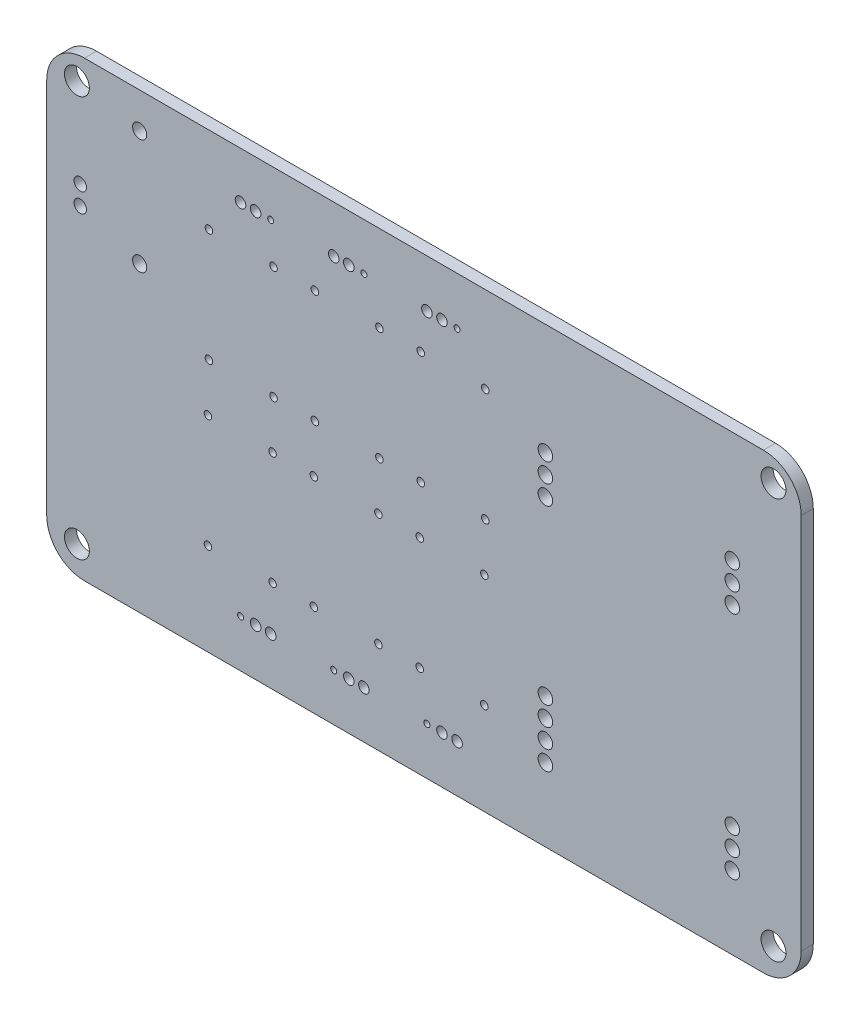
SolidWorks part; units mm, degrees
ref_plane "Front Plane" through (0, 0, 0) normal (0, 0, 1) x (1, 0, 0)
ref_plane "Top Plane" through (0, 0, 0) normal (0, 1, 0) x (1, 0, 0)
ref_plane "Right Plane" through (0, 0, 0) normal (1, 0, 0) x (0, 0, -1)
sketch "BoardOutLine" plane through (0, 0, 0) normal (0, 0, 1) x (1, 0, 0)
  line L0 (0, -55) -> (0, -5)
  line L1 (100, -5) -> (100, -55)
  line L2 (95, -60) -> (5, -60)
  line L3 (5, 0) -> (95, 0)
  line L4 (5, -5) -> (95, -55) construction
  line L6 (95, -5) -> (5, -55) construction
  arc A0 (100, -5) -> (95, 0) centre (95, -5) ccw
  arc A1 (0, -55) -> (5, -60) centre (5, -55) ccw
  arc A2 (5, 0) -> (0, -5) centre (5, -5) ccw
  arc A3 (95, -60) -> (100, -55) centre (95, -55) ccw
  dimension "D1" = 5
  dimension "D2" = 90
  dimension "D3" = 50
  dimension "D4" = 5
  dimension "D5" = 5
extrude "Boss-Extrude2" add sketch "BoardOutLine" along normal blind 1.6
sketch "Multi-Layer" plane through (0, 0, 1.6) normal (0, 0, 1) x (1, 0, 0)
  circle A1 centre (12.319, -4.699) radius 0.9398
  circle A3 centre (12.319, -19.939) radius 0.9398
  circle A5 centre (4.445, -14.732) radius 0.8255
  circle A7 centre (4.445, -17.272) radius 0.8255
  circle A10 centre (90.8641, -50.3084) radius 0.9652
  circle A13 centre (90.8641, -47.7684) radius 0.9652
  circle A16 centre (90.8641, -45.2283) radius 0.9652
  circle A46 centre (90.8641, -19.8283) radius 0.9652
  circle A49 centre (90.8641, -17.2883) radius 0.9652
  circle A52 centre (90.8641, -14.7483) radius 0.9652
  circle A55 centre (66.094, -14.7483) radius 0.9652
  circle A58 centre (66.094, -17.2883) radius 0.9652
  circle A61 centre (66.094, -19.8283) radius 0.9652
  circle A88 centre (66.094, -42.6883) radius 0.9652
  circle A91 centre (66.094, -45.2283) radius 0.9652
  circle A94 centre (66.094, -47.7684) radius 0.9652
  circle A97 centre (66.094, -50.3084) radius 0.9652
  circle A127 centre (40.0368, -6.223) radius 0.7
  circle A129 centre (38.0368, -6.223) radius 0.7
  circle A131 centre (52.3876, -6.35) radius 0.7
  circle A133 centre (50.3876, -6.35) radius 0.7
  circle A135 centre (40.0368, -53.7211) radius 0.7
  circle A137 centre (42.0368, -53.7211) radius 0.7
  circle A139 centre (52.3876, -53.7211) radius 0.7
  circle A141 centre (54.3876, -53.7211) radius 0.7
  circle A143 centre (27.6861, -6.223) radius 0.7
  circle A145 centre (25.6861, -6.223) radius 0.7
  circle A147 centre (27.6861, -53.7211) radius 0.7
  circle A149 centre (29.6861, -53.7211) radius 0.7
  circle A150 centre (44.0961, -11.4149) radius 0.5
  circle A151 centre (35.5373, -11.4149) radius 0.5
  circle A152 centre (44.0961, -26.3802) radius 0.5
  circle A153 centre (35.5373, -26.3802) radius 0.5
  circle A154 centre (58.1296, -11.4149) radius 0.5
  circle A155 centre (49.5708, -11.4149) radius 0.5
  circle A156 centre (58.1296, -26.3802) radius 0.5
  circle A157 centre (49.5708, -26.3802) radius 0.5
  circle A158 centre (30.0626, -11.4149) radius 0.5
  circle A159 centre (21.5038, -11.4149) radius 0.5
  circle A160 centre (30.0626, -26.3802) radius 0.5
  circle A161 centre (21.5038, -26.3802) radius 0.5
  circle A162 centre (49.4396, -47.7672) radius 0.5
  circle A163 centre (57.9984, -47.7672) radius 0.5
  circle A164 centre (49.4396, -32.802) radius 0.5
  circle A165 centre (57.9984, -32.802) radius 0.5
  circle A166 centre (35.406, -47.7672) radius 0.5
  circle A167 centre (43.9648, -47.7672) radius 0.5
  circle A168 centre (35.406, -32.802) radius 0.5
  circle A169 centre (43.9648, -32.802) radius 0.5
  circle A170 centre (21.3725, -47.7672) radius 0.5
  circle A171 centre (29.9313, -47.7672) radius 0.5
  circle A172 centre (21.3725, -32.802) radius 0.5
  circle A173 centre (29.9313, -32.802) radius 0.5
  circle A181 centre (42.0368, -6.223) radius 0.4
  circle A182 centre (54.3876, -6.35) radius 0.4
  circle A183 centre (38.0368, -53.7211) radius 0.4
  circle A184 centre (50.3876, -53.7211) radius 0.4
  circle A185 centre (29.6861, -6.223) radius 0.4
  circle A186 centre (25.6861, -53.7211) radius 0.4
  circle A187 centre (96.3297, -3.1115) radius 1.65
  circle A188 centre (4.0005, -3.1115) radius 1.65
  circle A189 centre (96.3297, -56.2611) radius 1.65
  circle A190 centre (4.0005, -56.2611) radius 1.65
  point P1 (0, 0)
  point P4 (0, 0)
  point P12 (0, 0)
  point P15 (0, 0)
  point P20 (0, 0)
  point P23 (0, 0)
  point P28 (0, 0)
  point P108 (0, 0)
  point P116 (0, 0)
  point P220 (0, 0)
  point P223 (0, 0)
  point P228 (0, 0)
  point P231 (0, 0)
  point P236 (0, 0)
  point P239 (0, 0)
  point P244 (0, 0)
  point P307 (0, 0)
  point P310 (0, 0)
  point P325 (0, 0)
extrude "Cut-Extrude2" cut sketch "Multi-Layer" against normal up to next (1.6 mm away)
sketch "BottomLayer" plane through (0, 0, 0) normal (0, 0, 1) x (1, 0, 0)
  line L0 (65.2082, -47.5949) -> (65.3816, -47.7684)
  line L2 (49.5708, -11.4148) -> (52.4663, -11.4148)
  line L3 (52.4663, -11.4148) -> (54.3876, -9.4935)
  line L4 (54.3876, -9.4935) -> (54.3876, -6.35)
  line L5 (29.9313, -32.8019) -> (30.5944, -34.4044)
  line L6 (30.5944, -34.4044) -> (32.8931, -36.7031)
  line L7 (32.8931, -36.7031) -> (42.2911, -36.7031)
  line L8 (42.2911, -36.7031) -> (43.3071, -35.6871)
  line L9 (43.3071, -35.6871) -> (43.9648, -32.8019)
  line L10 (43.9648, -32.8019) -> (44.0691, -35.6871)
  line L11 (44.0691, -35.6871) -> (44.9581, -36.7031)
  line L12 (44.9581, -36.7031) -> (56.1341, -36.7031)
  line L13 (56.1341, -36.7031) -> (58.0391, -34.5441)
  line L14 (58.0391, -34.5441) -> (57.9984, -32.8019)
  line L15 (29.9313, -47.7673) -> (27.1628, -47.7673)
  line L16 (27.1628, -47.7673) -> (25.6871, -49.2431)
  line L17 (25.6871, -49.2431) -> (25.6871, -53.7211)
  line L18 (57.9984, -47.7673) -> (53.5789, -47.7673)
  line L19 (53.5789, -47.7673) -> (50.3886, -50.9576)
  line L20 (50.3886, -50.9576) -> (50.3886, -53.7211)
  line L21 (49.5708, -26.3802) -> (49.5708, -11.4148)
  line L22 (57.9984, -47.7673) -> (57.9984, -32.8019)
  line L23 (43.9648, -32.8019) -> (43.9648, -47.7673)
  line L24 (29.9313, -47.7673) -> (29.9313, -32.8019)
  line L25 (35.5373, -26.3802) -> (38.3312, -23.114)
  line L26 (38.3312, -23.114) -> (46.0224, -23.114)
  line L27 (46.0224, -23.114) -> (49.5708, -26.3802)
  line L28 (21.5038, -26.3802) -> (24.8692, -22.352)
  line L29 (24.8692, -22.352) -> (31.0363, -22.352)
  line L30 (31.0363, -22.352) -> (35.5373, -26.3802)
  line L31 (35.5373, -26.3802) -> (35.5373, -11.4148)
  line L32 (21.5038, -26.3802) -> (21.5038, -11.4148)
  line L33 (57.9984, -47.7673) -> (57.9994, -47.7684)
  line L34 (57.9994, -47.7684) -> (66.094, -47.7684)
  line L35 (52.3876, -53.7211) -> (52.3876, -52.1336)
  line L36 (52.3876, -52.1336) -> (54.2129, -50.3084)
  line L37 (54.2129, -50.3084) -> (66.094, -50.3084)
  line L38 (21.5038, -26.3802) -> (16.5456, -26.3805)
  line L39 (16.5456, -26.3805) -> (14.5568, -28.3693)
  line L40 (14.5568, -28.3693) -> (14.5568, -29.7816)
  line L41 (14.5568, -29.7816) -> (14.5568, -31.4478)
  line L42 (14.5568, -31.4478) -> (19.304, -36.1951)
  line L43 (19.304, -36.1951) -> (28.0467, -36.1951)
  line L44 (28.0467, -36.1951) -> (29.9416, -34.3002)
  line L45 (29.9416, -34.3002) -> (29.9313, -32.8019)
  line L46 (14.5568, -29.7816) -> (4.445, -19.6694)
  line L47 (4.445, -19.6694) -> (4.445, -17.272)
  line L48 (21.5038, -11.4148) -> (26.0503, -11.4148)
  line L49 (26.0503, -11.4148) -> (29.685, -7.78)
  line L50 (29.685, -7.78) -> (29.685, -6.223)
  line L51 (43.9648, -47.7673) -> (40.2438, -47.7673)
  line L52 (40.2438, -47.7673) -> (38.1001, -50.2921)
  line L53 (38.1001, -50.2921) -> (38.0368, -53.7211)
  line L54 (35.5373, -11.4148) -> (39.2583, -11.4148)
  line L55 (39.2583, -11.4148) -> (42.0371, -8.636)
  line L56 (42.0371, -8.636) -> (42.0371, -6.223)
sketch "BottomSilkLayer" plane through (0, 0, 0) normal (0, 0, 1) x (1, 0, 0)
  line L0 (82.4232, -18.034) -> (82.4232, -44.5136) construction
  line L1 (78.6132, -22.225) -> (78.6132, -40.5131) construction
  text T0 "Manipulator Board V1" font "ARIAL" height 2.032
  text T1 "Tamir Mhabary" font "ARIAL" height 2.032
sketch "BottomSolderMaskLayer" plane through (0, 0, 0) normal (0, 0, 1) x (1, 0, 0)
  line L0 (90.351, -50.3081) -> (90.351, -50.3084)
  line L1 (90.351, -50.3084) -> (90.351, -50.3081)
  line L2 (91.377, -50.3081) -> (91.377, -50.3084)
  line L3 (91.377, -50.3084) -> (91.377, -50.3081)
  line L4 (90.351, -47.7681) -> (90.351, -47.7684)
  line L5 (90.351, -47.7684) -> (90.351, -47.7681)
  line L6 (91.377, -47.7681) -> (91.377, -47.7684)
  line L7 (91.377, -47.7684) -> (91.377, -47.7681)
  line L8 (90.351, -45.2281) -> (90.351, -45.2283)
  line L9 (90.351, -45.2283) -> (90.351, -45.2281)
  line L10 (91.377, -45.2281) -> (91.377, -45.2283)
  line L11 (91.377, -45.2283) -> (91.377, -45.2281)
  line L12 (90.351, -42.6881) -> (90.351, -42.6883)
  line L13 (90.351, -42.6883) -> (90.351, -42.6881)
  line L14 (91.377, -42.6881) -> (91.377, -42.6883)
  line L15 (91.377, -42.6883) -> (91.377, -42.6881)
  line L16 (90.351, -40.1481) -> (90.351, -40.1483)
  line L17 (90.351, -40.1483) -> (90.351, -40.1481)
  line L18 (91.377, -40.1481) -> (91.377, -40.1483)
  line L19 (91.377, -40.1483) -> (91.377, -40.1481)
  line L20 (90.351, -37.6081) -> (90.351, -37.6083)
  line L21 (90.351, -37.6083) -> (90.351, -37.6081)
  line L22 (91.377, -37.6081) -> (91.377, -37.6083)
  line L23 (91.377, -37.6083) -> (91.377, -37.6081)
  line L24 (90.351, -35.0681) -> (90.351, -35.0683)
  line L25 (90.351, -35.0683) -> (90.351, -35.0681)
  line L26 (91.377, -35.0681) -> (91.377, -35.0683)
  line L27 (91.377, -35.0683) -> (91.377, -35.0681)
  line L28 (90.351, -32.5281) -> (90.351, -32.5283)
  line L29 (90.351, -32.5283) -> (90.351, -32.5281)
  line L30 (91.377, -32.5281) -> (91.377, -32.5283)
  line L31 (91.377, -32.5283) -> (91.377, -32.5281)
  line L32 (90.351, -29.9881) -> (90.351, -29.9883)
  line L33 (90.351, -29.9883) -> (90.351, -29.9881)
  line L34 (91.377, -29.9881) -> (91.377, -29.9883)
  line L35 (91.377, -29.9883) -> (91.377, -29.9881)
  line L36 (90.351, -27.4481) -> (90.351, -27.4483)
  line L37 (90.351, -27.4483) -> (90.351, -27.4481)
  line L38 (91.377, -27.4481) -> (91.377, -27.4483)
  line L39 (91.377, -27.4483) -> (91.377, -27.4481)
  line L40 (90.351, -24.908) -> (90.351, -24.9083)
  line L41 (90.351, -24.9083) -> (90.351, -24.908)
  line L42 (91.377, -24.908) -> (91.377, -24.9083)
  line L43 (91.377, -24.9083) -> (91.377, -24.908)
  line L44 (90.351, -22.368) -> (90.351, -22.3683)
  line L45 (90.351, -22.3683) -> (90.351, -22.368)
  line L46 (91.377, -22.368) -> (91.377, -22.3683)
  line L47 (91.377, -22.3683) -> (91.377, -22.368)
  line L48 (90.351, -19.828) -> (90.351, -19.8283)
  line L49 (90.351, -19.8283) -> (90.351, -19.828)
  line L50 (91.377, -19.828) -> (91.377, -19.8283)
  line L51 (91.377, -19.8283) -> (91.377, -19.828)
  line L52 (90.351, -17.288) -> (90.351, -17.2883)
  line L53 (90.351, -17.2883) -> (90.351, -17.288)
  line L54 (91.377, -17.288) -> (91.377, -17.2883)
  line L55 (91.377, -17.2883) -> (91.377, -17.288)
  line L56 (90.351, -14.748) -> (90.351, -14.7483)
  line L57 (90.351, -14.7483) -> (90.351, -14.748)
  line L58 (91.377, -14.748) -> (91.377, -14.7483)
  line L59 (91.377, -14.7483) -> (91.377, -14.748)
  line L60 (65.5808, -14.748) -> (65.5808, -14.7483)
  line L61 (65.5808, -14.7483) -> (65.5808, -14.748)
  line L62 (66.6069, -14.748) -> (66.6069, -14.7483)
  line L63 (66.6069, -14.7483) -> (66.6069, -14.748)
  line L64 (65.5808, -17.288) -> (65.5808, -17.2883)
  line L65 (65.5808, -17.2883) -> (65.5808, -17.288)
  line L66 (66.6069, -17.288) -> (66.6069, -17.2883)
  line L67 (66.6069, -17.2883) -> (66.6069, -17.288)
  line L68 (65.5808, -19.828) -> (65.5808, -19.8283)
  line L69 (65.5808, -19.8283) -> (65.5808, -19.828)
  line L70 (66.6069, -19.828) -> (66.6069, -19.8283)
  line L71 (66.6069, -19.8283) -> (66.6069, -19.828)
  line L72 (65.5808, -22.368) -> (65.5808, -22.3683)
  line L73 (65.5808, -22.3683) -> (65.5808, -22.368)
  line L74 (66.6069, -22.368) -> (66.6069, -22.3683)
  line L75 (66.6069, -22.3683) -> (66.6069, -22.368)
  line L76 (65.5808, -24.908) -> (65.5808, -24.9083)
  line L77 (65.5808, -24.9083) -> (65.5808, -24.908)
  line L78 (66.6069, -24.908) -> (66.6069, -24.9083)
  line L79 (66.6069, -24.9083) -> (66.6069, -24.908)
  line L80 (65.5808, -27.4481) -> (65.5808, -27.4483)
  line L81 (65.5808, -27.4483) -> (65.5808, -27.4481)
  line L82 (66.6069, -27.4481) -> (66.6069, -27.4483)
  line L83 (66.6069, -27.4483) -> (66.6069, -27.4481)
  line L84 (65.5808, -29.9881) -> (65.5808, -29.9883)
  line L85 (65.5808, -29.9883) -> (65.5808, -29.9881)
  line L86 (66.6069, -29.9881) -> (66.6069, -29.9883)
  line L87 (66.6069, -29.9883) -> (66.6069, -29.9881)
  line L88 (65.5808, -32.5281) -> (65.5808, -32.5283)
  line L89 (65.5808, -32.5283) -> (65.5808, -32.5281)
  line L90 (66.6069, -32.5281) -> (66.6069, -32.5283)
  line L91 (66.6069, -32.5283) -> (66.6069, -32.5281)
  line L92 (65.5808, -35.0681) -> (65.5808, -35.0683)
  line L93 (65.5808, -35.0683) -> (65.5808, -35.0681)
  line L94 (66.6069, -35.0681) -> (66.6069, -35.0683)
  line L95 (66.6069, -35.0683) -> (66.6069, -35.0681)
  line L96 (65.5808, -37.6081) -> (65.5808, -37.6083)
  line L97 (65.5808, -37.6083) -> (65.5808, -37.6081)
  line L98 (66.6069, -37.6081) -> (66.6069, -37.6083)
  line L99 (66.6069, -37.6083) -> (66.6069, -37.6081)
  line L100 (65.5808, -40.1481) -> (65.5808, -40.1483)
  line L101 (65.5808, -40.1483) -> (65.5808, -40.1481)
  line L102 (66.6069, -40.1481) -> (66.6069, -40.1483)
  line L103 (66.6069, -40.1483) -> (66.6069, -40.1481)
  line L104 (65.5808, -42.6881) -> (65.5808, -42.6883)
  line L105 (65.5808, -42.6883) -> (65.5808, -42.6881)
  line L106 (66.6069, -42.6881) -> (66.6069, -42.6883)
  line L107 (66.6069, -42.6883) -> (66.6069, -42.6881)
  line L108 (65.5808, -45.2281) -> (65.5808, -45.2283)
  line L109 (65.5808, -45.2283) -> (65.5808, -45.2281)
  line L110 (66.6069, -45.2281) -> (66.6069, -45.2283)
  line L111 (66.6069, -45.2283) -> (66.6069, -45.2281)
  line L112 (65.5808, -47.7681) -> (65.5808, -47.7684)
  line L113 (65.5808, -47.7684) -> (65.5808, -47.7681)
  line L114 (66.6069, -47.7681) -> (66.6069, -47.7684)
  line L115 (66.6069, -47.7684) -> (66.6069, -47.7681)
  line L116 (65.5808, -50.3081) -> (65.5808, -50.3084)
  line L117 (65.5808, -50.3084) -> (65.5808, -50.3081)
  line L118 (66.6069, -50.3081) -> (66.6069, -50.3084)
  line L119 (66.6069, -50.3084) -> (66.6069, -50.3081)
  line L120 (13.0713, -34.0756) -> (11.0431, -34.0756)
  line L121 (11.0431, -34.0756) -> (13.0713, -34.0756)
  line L122 (13.0713, -34.8868) -> (11.0431, -34.8868)
  line L123 (11.0431, -34.8868) -> (13.0713, -34.8868)
  line L124 (8.1444, -30.8956) -> (8.1444, -28.6662)
  line L125 (8.1444, -28.6662) -> (8.1444, -30.8956)
  line L126 (8.9698, -30.8956) -> (8.9698, -28.6662)
  line L127 (8.9698, -28.6662) -> (8.9698, -30.8956)
  line L128 (14.1441, -28.6663) -> (14.1441, -30.8958)
  line L129 (14.1441, -30.8958) -> (14.1441, -28.6663)
  line L130 (14.9695, -28.6663) -> (14.9695, -30.8958)
  line L131 (14.9695, -30.8958) -> (14.9695, -28.6663)
  circle A0 centre (12.319, -4.699) radius 0.6156
  circle A1 centre (12.319, -4.699) radius 0.9652
  circle A2 centre (12.319, -19.939) radius 0.6156
  circle A3 centre (12.319, -19.939) radius 0.9652
  circle A4 centre (4.445, -14.732) radius 0.4639
  circle A5 centre (4.445, -14.732) radius 0.8509
  circle A6 centre (4.445, -17.272) radius 0.4639
  circle A7 centre (4.445, -17.272) radius 0.8509
  arc A8 (90.351, -50.3084) -> (91.377, -50.3084) centre (90.864, -50.3084) ccw
  arc A9 (91.377, -50.3081) -> (90.351, -50.3081) centre (90.864, -50.3081) ccw
  circle A10 centre (90.8641, -50.3084) radius 0.9906
  arc A11 (90.351, -47.7684) -> (91.377, -47.7684) centre (90.864, -47.7684) ccw
  arc A12 (91.377, -47.7681) -> (90.351, -47.7681) centre (90.864, -47.7681) ccw
  circle A13 centre (90.8641, -47.7684) radius 0.9906
  arc A14 (90.351, -45.2283) -> (91.377, -45.2283) centre (90.864, -45.2283) ccw
  arc A15 (91.377, -45.2281) -> (90.351, -45.2281) centre (90.864, -45.2281) ccw
  circle A16 centre (90.8641, -45.2283) radius 0.9906
  arc A17 (90.351, -42.6883) -> (91.377, -42.6883) centre (90.864, -42.6883) ccw
  arc A18 (91.377, -42.6881) -> (90.351, -42.6881) centre (90.864, -42.6881) ccw
  circle A19 centre (90.8641, -42.6883) radius 0.9906
  arc A20 (90.351, -40.1483) -> (91.377, -40.1483) centre (90.864, -40.1483) ccw
  arc A21 (91.377, -40.1481) -> (90.351, -40.1481) centre (90.864, -40.1481) ccw
  circle A22 centre (90.8641, -40.1483) radius 0.9906
  arc A23 (90.351, -37.6083) -> (91.377, -37.6083) centre (90.864, -37.6083) ccw
  arc A24 (91.377, -37.6081) -> (90.351, -37.6081) centre (90.864, -37.6081) ccw
  circle A25 centre (90.8641, -37.6083) radius 0.9906
  arc A26 (90.351, -35.0683) -> (91.377, -35.0683) centre (90.864, -35.0683) ccw
  arc A27 (91.377, -35.0681) -> (90.351, -35.0681) centre (90.864, -35.0681) ccw
  circle A28 centre (90.8641, -35.0683) radius 0.9906
  arc A29 (90.351, -32.5283) -> (91.377, -32.5283) centre (90.864, -32.5283) ccw
  arc A30 (91.377, -32.5281) -> (90.351, -32.5281) centre (90.864, -32.5281) ccw
  circle A31 centre (90.8641, -32.5283) radius 0.9906
  arc A32 (90.351, -29.9883) -> (91.377, -29.9883) centre (90.864, -29.9883) ccw
  arc A33 (91.377, -29.9881) -> (90.351, -29.9881) centre (90.864, -29.9881) ccw
  circle A34 centre (90.8641, -29.9883) radius 0.9906
  arc A35 (90.351, -27.4483) -> (91.377, -27.4483) centre (90.864, -27.4483) ccw
  arc A36 (91.377, -27.4481) -> (90.351, -27.4481) centre (90.864, -27.4481) ccw
  circle A37 centre (90.8641, -27.4483) radius 0.9906
  arc A38 (90.351, -24.9083) -> (91.377, -24.9083) centre (90.864, -24.9083) ccw
  arc A39 (91.377, -24.908) -> (90.351, -24.908) centre (90.864, -24.908) ccw
  circle A40 centre (90.8641, -24.9083) radius 0.9906
  arc A41 (90.351, -22.3683) -> (91.377, -22.3683) centre (90.864, -22.3683) ccw
  arc A42 (91.377, -22.368) -> (90.351, -22.368) centre (90.864, -22.368) ccw
  circle A43 centre (90.8641, -22.3683) radius 0.9906
  arc A44 (90.351, -19.8283) -> (91.377, -19.8283) centre (90.864, -19.8283) ccw
  arc A45 (91.377, -19.828) -> (90.351, -19.828) centre (90.864, -19.828) ccw
  circle A46 centre (90.8641, -19.8283) radius 0.9906
  arc A47 (90.351, -17.2883) -> (91.377, -17.2883) centre (90.864, -17.2883) ccw
  arc A48 (91.377, -17.288) -> (90.351, -17.288) centre (90.864, -17.288) ccw
  circle A49 centre (90.8641, -17.2883) radius 0.9906
  arc A50 (90.351, -14.7483) -> (91.377, -14.7483) centre (90.864, -14.7483) ccw
  arc A51 (91.377, -14.748) -> (90.351, -14.748) centre (90.864, -14.748) ccw
  circle A52 centre (90.8641, -14.7483) radius 0.9906
  arc A53 (65.5808, -14.7483) -> (66.6069, -14.7483) centre (66.0938, -14.7483) ccw
  arc A54 (66.6069, -14.748) -> (65.5808, -14.748) centre (66.0938, -14.748) ccw
  circle A55 centre (66.094, -14.7483) radius 0.9906
  arc A56 (65.5808, -17.2883) -> (66.6069, -17.2883) centre (66.0938, -17.2883) ccw
  arc A57 (66.6069, -17.288) -> (65.5808, -17.288) centre (66.0938, -17.288) ccw
  circle A58 centre (66.094, -17.2883) radius 0.9906
  arc A59 (65.5808, -19.8283) -> (66.6069, -19.8283) centre (66.0938, -19.8283) ccw
  arc A60 (66.6069, -19.828) -> (65.5808, -19.828) centre (66.0938, -19.828) ccw
  circle A61 centre (66.094, -19.8283) radius 0.9906
  arc A62 (65.5808, -22.3683) -> (66.6069, -22.3683) centre (66.0938, -22.3683) ccw
  arc A63 (66.6069, -22.368) -> (65.5808, -22.368) centre (66.0938, -22.368) ccw
  circle A64 centre (66.094, -22.3683) radius 0.9906
  arc A65 (65.5808, -24.9083) -> (66.6069, -24.9083) centre (66.0938, -24.9083) ccw
  arc A66 (66.6069, -24.908) -> (65.5808, -24.908) centre (66.0938, -24.908) ccw
  circle A67 centre (66.094, -24.9083) radius 0.9906
  arc A68 (65.5808, -27.4483) -> (66.6069, -27.4483) centre (66.0938, -27.4483) ccw
  arc A69 (66.6069, -27.4481) -> (65.5808, -27.4481) centre (66.0938, -27.4481) ccw
  circle A70 centre (66.094, -27.4483) radius 0.9906
  arc A71 (65.5808, -29.9883) -> (66.6069, -29.9883) centre (66.0938, -29.9883) ccw
  arc A72 (66.6069, -29.9881) -> (65.5808, -29.9881) centre (66.0938, -29.9881) ccw
  circle A73 centre (66.094, -29.9883) radius 0.9906
  arc A74 (65.5808, -32.5283) -> (66.6069, -32.5283) centre (66.0938, -32.5283) ccw
  arc A75 (66.6069, -32.5281) -> (65.5808, -32.5281) centre (66.0938, -32.5281) ccw
  circle A76 centre (66.094, -32.5283) radius 0.9906
  arc A77 (65.5808, -35.0683) -> (66.6069, -35.0683) centre (66.0938, -35.0683) ccw
  arc A78 (66.6069, -35.0681) -> (65.5808, -35.0681) centre (66.0938, -35.0681) ccw
  circle A79 centre (66.094, -35.0683) radius 0.9906
  arc A80 (65.5808, -37.6083) -> (66.6069, -37.6083) centre (66.0938, -37.6083) ccw
  arc A81 (66.6069, -37.6081) -> (65.5808, -37.6081) centre (66.0938, -37.6081) ccw
  circle A82 centre (66.094, -37.6083) radius 0.9906
  arc A83 (65.5808, -40.1483) -> (66.6069, -40.1483) centre (66.0938, -40.1483) ccw
  arc A84 (66.6069, -40.1481) -> (65.5808, -40.1481) centre (66.0938, -40.1481) ccw
  circle A85 centre (66.094, -40.1483) radius 0.9906
  arc A86 (65.5808, -42.6883) -> (66.6069, -42.6883) centre (66.0938, -42.6883) ccw
  arc A87 (66.6069, -42.6881) -> (65.5808, -42.6881) centre (66.0938, -42.6881) ccw
  circle A88 centre (66.094, -42.6883) radius 0.9906
  arc A89 (65.5808, -45.2283) -> (66.6069, -45.2283) centre (66.0938, -45.2283) ccw
  arc A90 (66.6069, -45.2281) -> (65.5808, -45.2281) centre (66.0938, -45.2281) ccw
  circle A91 centre (66.094, -45.2283) radius 0.9906
  arc A92 (65.5808, -47.7684) -> (66.6069, -47.7684) centre (66.0938, -47.7684) ccw
  arc A93 (66.6069, -47.7681) -> (65.5808, -47.7681) centre (66.0938, -47.7681) ccw
  circle A94 centre (66.094, -47.7684) radius 0.9906
  arc A95 (65.5808, -50.3084) -> (66.6069, -50.3084) centre (66.0938, -50.3084) ccw
  arc A96 (66.6069, -50.3081) -> (65.5808, -50.3081) centre (66.0938, -50.3081) ccw
  circle A97 centre (66.094, -50.3084) radius 0.9906
  circle A98 centre (94.6152, -50.2921) radius 0.4588
  circle A99 centre (94.6152, -50.2921) radius 0.8128
  circle A100 centre (94.6152, -47.7521) radius 0.4588
  circle A101 centre (94.6152, -47.7521) radius 0.8128
  circle A102 centre (94.6152, -45.2121) radius 0.4588
  circle A103 centre (94.6152, -45.2121) radius 0.8128
  circle A104 centre (94.6152, -42.6721) radius 0.4588
  circle A105 centre (94.6152, -42.6721) radius 0.8128
  circle A106 centre (94.6152, -40.1321) radius 0.4588
  circle A107 centre (94.6152, -40.1321) radius 0.8128
  circle A108 centre (94.6152, -37.5921) radius 0.4588
  circle A109 centre (94.6152, -37.5921) radius 0.8128
  circle A110 centre (94.6152, -35.0521) radius 0.4588
  circle A111 centre (94.6152, -35.0521) radius 0.8128
  circle A112 centre (94.6152, -32.5121) radius 0.4588
  circle A113 centre (94.6152, -32.5121) radius 0.8128
  circle A114 centre (94.6152, -29.9721) radius 0.4588
  circle A115 centre (94.6152, -29.9721) radius 0.8128
  circle A116 centre (94.6152, -27.4321) radius 0.4588
  circle A117 centre (94.6152, -27.4321) radius 0.8128
  circle A118 centre (94.6152, -24.892) radius 0.4588
  circle A119 centre (94.6152, -24.892) radius 0.8128
  circle A120 centre (94.6152, -22.352) radius 0.4588
  circle A121 centre (94.6152, -22.352) radius 0.8128
  circle A122 centre (94.6152, -19.812) radius 0.4588
  circle A123 centre (94.6152, -19.812) radius 0.8128
  circle A124 centre (94.6152, -17.272) radius 0.4588
  circle A125 centre (94.6152, -17.272) radius 0.8128
  circle A126 centre (40.0368, -6.223) radius 0.4143
  circle A127 centre (40.0368, -6.223) radius 0.725
  circle A128 centre (38.0368, -6.223) radius 0.4143
  circle A129 centre (38.0368, -6.223) radius 0.725
  circle A130 centre (52.3876, -6.35) radius 0.4143
  circle A131 centre (52.3876, -6.35) radius 0.725
  circle A132 centre (50.3876, -6.35) radius 0.4143
  circle A133 centre (50.3876, -6.35) radius 0.725
  circle A134 centre (40.0368, -53.7211) radius 0.4143
  circle A135 centre (40.0368, -53.7211) radius 0.725
  circle A136 centre (42.0368, -53.7211) radius 0.4143
  circle A137 centre (42.0368, -53.7211) radius 0.725
  circle A138 centre (52.3876, -53.7211) radius 0.4143
  circle A139 centre (52.3876, -53.7211) radius 0.725
  circle A140 centre (54.3876, -53.7211) radius 0.4143
  circle A141 centre (54.3876, -53.7211) radius 0.725
  circle A142 centre (27.6861, -6.223) radius 0.4143
  circle A143 centre (27.6861, -6.223) radius 0.725
  circle A144 centre (25.6861, -6.223) radius 0.4143
  circle A145 centre (25.6861, -6.223) radius 0.725
  circle A146 centre (27.6861, -53.7211) radius 0.4143
  circle A147 centre (27.6861, -53.7211) radius 0.725
  circle A148 centre (29.6861, -53.7211) radius 0.4143
  circle A149 centre (29.6861, -53.7211) radius 0.725
  circle A150 centre (44.0961, -11.4149) radius 0.5254
  circle A151 centre (35.5373, -11.4149) radius 0.5254
  circle A152 centre (44.0961, -26.3802) radius 0.5254
  circle A153 centre (35.5373, -26.3802) radius 0.5254
  circle A154 centre (58.1296, -11.4149) radius 0.5254
  circle A155 centre (49.5708, -11.4149) radius 0.5254
  circle A156 centre (58.1296, -26.3802) radius 0.5254
  circle A157 centre (49.5708, -26.3802) radius 0.5254
  circle A158 centre (30.0626, -11.4149) radius 0.5254
  circle A159 centre (21.5038, -11.4149) radius 0.5254
  circle A160 centre (30.0626, -26.3802) radius 0.5254
  circle A161 centre (21.5038, -26.3802) radius 0.5254
  circle A162 centre (49.4396, -47.7672) radius 0.5254
  circle A163 centre (57.9984, -47.7672) radius 0.5254
  circle A164 centre (49.4396, -32.802) radius 0.5254
  circle A165 centre (57.9984, -32.802) radius 0.5254
  circle A166 centre (35.406, -47.7672) radius 0.5254
  circle A167 centre (43.9648, -47.7672) radius 0.5254
  circle A168 centre (35.406, -32.802) radius 0.5254
  circle A169 centre (43.9648, -32.802) radius 0.5254
  circle A170 centre (21.3725, -47.7672) radius 0.5254
  circle A171 centre (29.9313, -47.7672) radius 0.5254
  circle A172 centre (21.3725, -32.802) radius 0.5254
  circle A173 centre (29.9313, -32.802) radius 0.5254
  circle A174 centre (94.6152, -14.732) radius 0.4588
  arc A175 (11.0431, -34.0756) -> (11.0431, -34.8868) centre (11.0431, -34.4812) ccw
  arc A176 (13.0713, -34.8868) -> (13.0713, -34.0756) centre (13.0713, -34.4812) ccw
  arc A177 (8.9698, -30.8956) -> (8.1444, -30.8956) centre (8.5571, -30.8956) ccw
  arc A178 (8.1444, -28.6662) -> (8.9698, -28.6662) centre (8.5571, -28.6662) ccw
  arc A179 (14.1441, -28.6663) -> (14.9695, -28.6663) centre (14.5568, -28.6663) ccw
  arc A180 (14.9695, -30.8958) -> (14.1441, -30.8958) centre (14.5568, -30.8958) ccw
  circle A181 centre (42.0368, -6.223) radius 0.4143
  circle A182 centre (54.3876, -6.35) radius 0.4143
  circle A183 centre (38.0368, -53.7211) radius 0.4143
  circle A184 centre (50.3876, -53.7211) radius 0.4143
  circle A185 centre (29.6861, -6.223) radius 0.4143
  circle A186 centre (25.6861, -53.7211) radius 0.4143
sketch "TopLayer" plane through (0, 0, 0) normal (0, 0, 1) x (1, 0, 0)
  line L0 (27.6861, -53.7211) -> (27.6861, -50.0381)
  line L1 (27.6861, -50.0381) -> (25.4153, -47.7673)
  line L2 (25.4153, -47.7673) -> (21.3716, -47.7673)
  line L3 (49.4387, -47.7673) -> (51.0693, -47.7673)
  line L4 (51.0693, -47.7673) -> (52.3876, -49.0856)
  line L5 (52.3876, -49.0856) -> (52.3876, -53.7211)
  line L6 (35.4051, -32.8016) -> (35.4051, -35.2781)
  line L7 (35.4051, -35.2781) -> (36.8301, -36.7031)
  line L8 (36.8301, -36.7031) -> (47.6251, -36.7031)
  line L9 (47.6251, -36.7031) -> (49.4387, -34.8895)
  line L10 (49.4387, -34.8895) -> (49.4387, -32.8016)
  line L11 (21.3716, -32.8016) -> (21.3716, -35.3416)
  line L12 (21.3716, -35.3416) -> (22.733, -36.7031)
  line L13 (22.733, -36.7031) -> (33.9091, -36.7031)
  line L14 (33.9091, -36.7031) -> (35.4051, -35.207)
  line L15 (35.4051, -35.207) -> (35.4051, -32.8016)
  line L16 (8.5573, -29.7816) -> (8.5573, -24.4628)
  line L17 (8.5573, -24.4628) -> (10.16, -22.86)
  line L18 (10.16, -22.86) -> (28.8291, -22.86)
  line L19 (28.8291, -22.86) -> (30.0635, -24.0945)
  line L20 (30.0635, -24.0945) -> (30.0635, -26.3805)
  line L21 (29.4006, -11.4148) -> (28.4328, -11.4148)
  line L22 (28.4328, -11.4148) -> (27.6861, -10.668)
  line L23 (27.6861, -10.668) -> (27.6861, -6.223)
  line L24 (58.1306, -11.4148) -> (54.0869, -11.4148)
  line L25 (54.0869, -11.4148) -> (52.3876, -9.7155)
  line L26 (52.3876, -9.7155) -> (52.3876, -6.35)
  line L27 (64.1514, -32.1473) -> (62.8651, -30.8611)
  line L28 (62.8651, -30.8611) -> (62.8651, -6.223)
  line L29 (62.8651, -6.223) -> (58.8011, -2.159)
  line L30 (58.8011, -2.159) -> (28.3211, -2.159)
  line L31 (28.3211, -2.159) -> (25.9401, -4.54)
  line L32 (25.9401, -4.54) -> (25.9401, -6.223)
  line L33 (63.6424, -37.2263) -> (60.7061, -34.2901)
  line L34 (60.7061, -34.2901) -> (60.7061, -9.017)
  line L35 (60.7061, -9.017) -> (56.0071, -4.318)
  line L36 (56.0071, -4.318) -> (51.3081, -4.318)
  line L37 (51.3081, -4.318) -> (50.3251, -5.301)
  line L38 (50.3251, -5.301) -> (50.3251, -6.35)
  line L39 (90.8641, -14.7483) -> (94.5989, -14.7483)
  line L40 (94.5989, -14.7483) -> (94.6152, -14.732)
  line L41 (90.8641, -17.2883) -> (94.5989, -17.2883)
  line L42 (94.5989, -17.2883) -> (94.6152, -17.272)
  line L43 (90.8641, -19.8283) -> (94.5989, -19.8283)
  line L44 (94.5989, -19.8283) -> (94.6152, -19.812)
  line L45 (90.8641, -22.3683) -> (94.5989, -22.3683)
  line L46 (94.5989, -22.3683) -> (94.6152, -22.352)
  line L47 (90.8641, -24.9083) -> (94.5989, -24.9083)
  line L48 (94.5989, -24.9083) -> (94.6152, -24.892)
  line L49 (90.8641, -27.4483) -> (94.5989, -27.4483)
  line L50 (94.5989, -27.4483) -> (94.6152, -27.4321)
  line L51 (90.8641, -29.9883) -> (94.5989, -29.9883)
  line L52 (94.5989, -29.9883) -> (94.6152, -29.9721)
  line L53 (90.8641, -32.5283) -> (94.5989, -32.5283)
  line L54 (94.5989, -32.5283) -> (94.6152, -32.5121)
  line L55 (90.8641, -35.0683) -> (94.5989, -35.0683)
  line L56 (94.5989, -35.0683) -> (94.6152, -35.0521)
  line L57 (90.8641, -37.6083) -> (94.5989, -37.6083)
  line L58 (94.5989, -37.6083) -> (94.6152, -37.5921)
  line L59 (90.8641, -40.1483) -> (94.5989, -40.1483)
  line L60 (94.5989, -40.1483) -> (94.6152, -40.1321)
  line L61 (90.8641, -42.6883) -> (94.5989, -42.6883)
  line L62 (94.5989, -42.6883) -> (94.6152, -42.6721)
  line L63 (90.8641, -45.2283) -> (94.5989, -45.2283)
  line L64 (94.5989, -45.2283) -> (94.6152, -45.2121)
  line L65 (90.8641, -47.7684) -> (94.5989, -47.7684)
  line L66 (94.5989, -47.7684) -> (94.6152, -47.7521)
  line L67 (66.094, -32.5283) -> (64.5324, -32.5283)
  line L68 (64.5324, -32.5283) -> (64.1514, -32.1473)
  line L69 (66.094, -35.0683) -> (64.0244, -35.0683)
  line L70 (64.0244, -35.0683) -> (63.6434, -34.6873)
  line L71 (66.094, -37.6083) -> (64.0244, -37.6083)
  line L72 (64.0244, -37.6083) -> (63.6424, -37.2263)
  line L73 (90.8641, -50.3084) -> (94.5989, -50.3084)
  line L74 (94.5989, -50.3084) -> (94.6152, -50.2921)
  line L75 (66.0935, -45.2273) -> (64.6279, -45.2273)
  line L76 (64.6279, -45.2273) -> (63.5001, -46.3551)
  line L77 (63.5001, -46.3551) -> (63.5001, -53.9751)
  line L78 (63.5001, -53.9751) -> (59.5631, -57.9121)
  line L79 (59.5631, -57.9121) -> (32.0041, -57.9121)
  line L80 (32.0041, -57.9121) -> (29.431, -55.3391)
  line L81 (29.431, -55.3391) -> (29.431, -53.5941)
  line L82 (8.5573, -29.7816) -> (8.5573, -35.1003)
  line L83 (8.5573, -35.1003) -> (10.795, -37.3381)
  line L84 (10.795, -37.3381) -> (19.304, -37.3381)
  line L85 (19.304, -37.3381) -> (21.3716, -35.2705)
  line L86 (21.3716, -35.2705) -> (21.3716, -32.8016)
  line L87 (30.0635, -26.3805) -> (30.0559, -24.6965)
  line L88 (30.0559, -24.6965) -> (31.7653, -22.987)
  line L89 (31.7653, -22.987) -> (42.5451, -22.987)
  line L90 (42.5451, -22.987) -> (44.097, -24.539)
  line L91 (44.097, -24.539) -> (44.097, -26.3805)
  line L92 (44.097, -26.3805) -> (44.097, -24.9911)
  line L93 (44.097, -24.9911) -> (46.1011, -22.987)
  line L94 (46.1011, -22.987) -> (56.2611, -22.987)
  line L95 (56.2611, -22.987) -> (58.1306, -24.8565)
  line L96 (58.1306, -24.8565) -> (58.1306, -26.3805)
  line L97 (4.445, -14.732) -> (4.445, -9.906)
  line L98 (4.445, -9.906) -> (9.652, -4.699)
  line L99 (9.652, -4.699) -> (12.319, -4.699)
  line L100 (8.5573, -29.7816) -> (12.319, -26.0192)
  line L101 (12.319, -26.0192) -> (12.319, -19.939)
  line L102 (66.0935, -40.1473) -> (63.7389, -40.1473)
  line L103 (63.7389, -40.1473) -> (61.3411, -42.5451)
  line L104 (61.3411, -42.5451) -> (61.3411, -52.0701)
  line L105 (61.3411, -52.0701) -> (57.5311, -55.8801)
  line L106 (57.5311, -55.8801) -> (55.3721, -55.8801)
  line L107 (55.3721, -55.8801) -> (54.3866, -54.8946)
  line L108 (54.3866, -54.8946) -> (54.3866, -53.7211)
  line L109 (66.0935, -42.6873) -> (63.8964, -42.6746)
  line L110 (63.8964, -42.6746) -> (62.7381, -43.8303)
  line L111 (62.7381, -43.8303) -> (62.7381, -52.4511)
  line L112 (62.7381, -52.4511) -> (58.5471, -56.6421)
  line L113 (58.5471, -56.6421) -> (43.4341, -56.6421)
  line L114 (43.4341, -56.6421) -> (42.0371, -55.2451)
  line L115 (42.0371, -55.2451) -> (42.0371, -53.7211)
  line L116 (63.6424, -34.6863) -> (61.5951, -32.6391)
  line L117 (61.5951, -32.6391) -> (61.5951, -8.001)
  line L118 (61.5951, -8.001) -> (56.8961, -3.302)
  line L119 (56.8961, -3.302) -> (39.4971, -3.302)
  line L120 (39.4971, -3.302) -> (38.0366, -4.7625)
  line L121 (38.0366, -4.7625) -> (38.0366, -6.223)
  line L122 (35.4051, -47.7673) -> (37.2263, -47.7673)
  line L123 (37.2263, -47.7673) -> (40.0381, -50.5791)
  line L124 (40.0381, -50.5791) -> (40.0381, -53.7211)
  line L125 (44.097, -11.4148) -> (42.1488, -11.4148)
  line L126 (42.1488, -11.4148) -> (40.0381, -9.304)
  line L127 (40.0381, -9.304) -> (40.0381, -6.223)
sketch "TopSilkLayer" plane through (0, 0, 0) normal (0, 0, 1) x (1, 0, 0)
  line L0 (10.0584, -6.5786) -> (14.5796, -6.5786)
  line L1 (14.5796, -6.5786) -> (14.5796, -18.0594)
  line L2 (14.5796, -18.0594) -> (10.0584, -18.0594)
  line L3 (10.0584, -18.0594) -> (10.0584, -6.5786)
  line L4 (3.175, -17.6835) -> (5.7229, -17.6888)
  line L5 (64.624, -60.4383) -> (64.624, -8.4383)
  line L6 (64.624, -8.4383) -> (92.5239, -8.4383)
  line L7 (92.5239, -8.4383) -> (92.5239, -60.4383)
  line L8 (92.5239, -60.4383) -> (64.624, -60.4383)
  line L9 (39.4357, -15.2107) -> (39.4357, -25.2108)
  line L10 (45.6039, -10.0681) -> (45.6039, -27.7267)
  line L11 (45.6039, -27.7267) -> (33.8982, -27.7267)
  line L12 (33.8982, -27.7267) -> (33.8982, -10.0681)
  line L13 (33.8982, -10.0681) -> (45.6039, -10.0681)
  line L14 (53.4693, -15.2107) -> (53.4693, -25.2108)
  line L15 (59.6374, -10.0681) -> (59.6374, -27.7267)
  line L16 (59.6374, -27.7267) -> (47.9318, -27.7267)
  line L17 (47.9318, -27.7267) -> (47.9318, -10.0681)
  line L18 (47.9318, -10.0681) -> (59.6374, -10.0681)
  line L19 (25.4022, -15.2107) -> (25.4022, -25.2108)
  line L20 (31.5703, -10.0681) -> (31.5703, -27.7267)
  line L21 (31.5703, -27.7267) -> (19.8647, -27.7267)
  line L22 (19.8647, -27.7267) -> (19.8647, -10.0681)
  line L23 (19.8647, -10.0681) -> (31.5703, -10.0681)
  line L24 (54.0999, -43.9714) -> (54.0999, -33.9713)
  line L25 (47.9318, -49.114) -> (47.9318, -31.4554)
  line L26 (47.9318, -31.4554) -> (59.6374, -31.4554)
  line L27 (59.6374, -31.4554) -> (59.6374, -49.114)
  line L28 (59.6374, -49.114) -> (47.9318, -49.114)
  line L29 (40.0664, -43.9714) -> (40.0664, -33.9713)
  line L30 (33.8983, -49.114) -> (33.8983, -31.4554)
  line L31 (33.8983, -31.4554) -> (45.6039, -31.4554)
  line L32 (45.6039, -31.4554) -> (45.6039, -49.114)
  line L33 (45.6039, -49.114) -> (33.8983, -49.114)
  line L34 (26.0329, -43.9714) -> (26.0329, -33.9713)
  line L35 (19.8648, -49.114) -> (19.8648, -31.4554)
  line L36 (19.8648, -31.4554) -> (31.5704, -31.4554)
  line L37 (31.5704, -31.4554) -> (31.5704, -49.114)
  line L38 (31.5704, -49.114) -> (19.8648, -49.114)
  line L39 (95.8852, -51.5621) -> (93.3452, -51.5621)
  line L40 (93.3452, -51.5621) -> (93.3452, -13.462)
  line L41 (93.3452, -13.462) -> (95.8852, -13.462)
  line L42 (95.8852, -13.462) -> (95.8852, -15.367)
  line L43 (95.8852, -51.5621) -> (95.8852, -15.367)
  line L44 (10.0439, -34.2901) -> (1.057, -34.2901)
  line L45 (15.163, -31.7147) -> (15.163, -34.2901)
  line L46 (15.163, -34.2901) -> (14.0703, -34.2901)
  line L47 (1.057, -25.2808) -> (15.163, -25.2808)
  line L48 (15.163, -25.2808) -> (15.163, -27.8477)
  line L49 (1.057, -34.2808) -> (1.057, -25.2808)
  line L50 (4.5074, -34.2808) -> (4.5074, -25.2808)
  line L51 (4.5875, -32.9808) -> (15.2075, -32.9808)
  line L52 (4.5875, -26.581) -> (15.2075, -26.581)
  line L53 (42.968, -5.973) -> (43.1868, -5.973)
  line L54 (43.1868, -5.973) -> (43.1868, -7.573)
  line L55 (43.1868, -7.573) -> (43.9868, -7.573)
  line L56 (43.9868, -7.573) -> (43.9868, 0.027)
  line L57 (43.9868, 0.027) -> (36.0868, 0.027)
  line L58 (40.9337, -5.973) -> (41.1057, -5.973)
  line L59 (38.9337, -5.973) -> (39.14, -5.973)
  line L60 (36.0868, 0.027) -> (36.0868, -7.573)
  line L61 (36.0868, -7.573) -> (36.8868, -7.573)
  line L62 (36.8868, -7.573) -> (36.8868, -5.973)
  line L63 (36.8868, -5.973) -> (37.14, -5.973)
  line L64 (55.3187, -6.1) -> (55.5376, -6.1)
  line L65 (55.5376, -6.1) -> (55.5376, -7.7)
  line L66 (55.5376, -7.7) -> (56.3376, -7.7)
  line L67 (56.3376, -7.7) -> (56.3376, -0.1)
  line L68 (56.3376, -0.1) -> (48.4376, -0.1)
  line L69 (53.2845, -6.1) -> (53.4565, -6.1)
  line L70 (51.2845, -6.1) -> (51.4908, -6.1)
  line L71 (48.4376, -0.1) -> (48.4376, -7.7)
  line L72 (48.4376, -7.7) -> (49.2376, -7.7)
  line L73 (49.2376, -7.7) -> (49.2376, -6.1)
  line L74 (49.2376, -6.1) -> (49.4908, -6.1)
  line L75 (37.1057, -53.9711) -> (36.8868, -53.9711)
  line L76 (36.8868, -53.9711) -> (36.8868, -52.3711)
  line L77 (36.8868, -52.3711) -> (36.0868, -52.3711)
  line L78 (36.0868, -52.3711) -> (36.0868, -59.9711)
  line L79 (36.0868, -59.9711) -> (43.9868, -59.9711)
  line L80 (39.14, -53.9711) -> (38.968, -53.9711)
  line L81 (41.14, -53.9711) -> (40.9337, -53.9711)
  line L82 (43.9868, -59.9711) -> (43.9868, -52.3711)
  line L83 (43.9868, -52.3711) -> (43.1868, -52.3711)
  line L84 (43.1868, -52.3711) -> (43.1868, -53.9711)
  line L85 (43.1868, -53.9711) -> (42.9337, -53.9711)
  line L86 (49.4565, -53.9711) -> (49.2376, -53.9711)
  line L87 (49.2376, -53.9711) -> (49.2376, -52.3711)
  line L88 (49.2376, -52.3711) -> (48.4376, -52.3711)
  line L89 (48.4376, -52.3711) -> (48.4376, -59.9711)
  line L90 (48.4376, -59.9711) -> (56.3376, -59.9711)
  line L91 (51.4908, -53.9711) -> (51.3187, -53.9711)
  line L92 (53.4908, -53.9711) -> (53.2845, -53.9711)
  line L93 (56.3376, -59.9711) -> (56.3376, -52.3711)
  line L94 (56.3376, -52.3711) -> (55.5376, -52.3711)
  line L95 (55.5376, -52.3711) -> (55.5376, -53.9711)
  line L96 (55.5376, -53.9711) -> (55.2845, -53.9711)
  line L97 (30.6172, -5.973) -> (30.8361, -5.973)
  line L98 (30.8361, -5.973) -> (30.8361, -7.573)
  line L99 (30.8361, -7.573) -> (31.6361, -7.573)
  line L100 (31.6361, -7.573) -> (31.6361, 0.027)
  line L101 (31.6361, 0.027) -> (23.7361, 0.027)
  line L102 (28.5829, -5.973) -> (28.7549, -5.973)
  line L103 (26.5829, -5.973) -> (26.7892, -5.973)
  line L104 (23.7361, 0.027) -> (23.7361, -7.573)
  line L105 (23.7361, -7.573) -> (24.5361, -7.573)
  line L106 (24.5361, -7.573) -> (24.5361, -5.973)
  line L107 (24.5361, -5.973) -> (24.7892, -5.973)
  line L108 (24.7549, -53.9711) -> (24.536, -53.9711)
  line L109 (24.536, -53.9711) -> (24.536, -52.3711)
  line L110 (24.536, -52.3711) -> (23.736, -52.3711)
  line L111 (23.736, -52.3711) -> (23.736, -59.9711)
  line L112 (23.736, -59.9711) -> (31.636, -59.9711)
  line L113 (26.7892, -53.9711) -> (26.6172, -53.9711)
  line L114 (28.7892, -53.9711) -> (28.5829, -53.9711)
  line L115 (31.636, -59.9711) -> (31.636, -52.3711)
  line L116 (31.636, -52.3711) -> (30.836, -52.3711)
  line L117 (30.836, -52.3711) -> (30.836, -53.9711)
  line L118 (30.836, -53.9711) -> (30.5829, -53.9711)
  line L119 (99.1554, -14.0335) -> (96.2027, -14.0335) construction
  line L120 (99.1554, -16.5827) -> (96.2027, -16.5827) construction
  line L121 (98.6792, -21.6807) -> (96.4884, -21.6807) construction
  line L122 (98.9472, -24.2299) -> (95.9944, -24.2299) construction
  line L123 (98.9243, -26.779) -> (95.9716, -26.779) construction
  line L124 (98.9472, -29.3279) -> (95.9944, -29.3279) construction
  line L125 (98.6792, -31.8771) -> (96.4884, -31.8771) construction
  line L126 (98.9243, -36.9751) -> (95.9716, -36.9751) construction
  line L127 (98.7033, -39.5243) -> (96.5126, -39.5243) construction
  line L128 (98.6792, -42.0734) -> (96.4884, -42.0734) construction
  line L129 (98.9802, -47.1715) -> (95.9639, -47.1715) construction
  line L130 (98.4722, -19.1316) -> (96.2814, -19.1316) construction
  line L131 (98.9469, -34.4262) -> (95.9942, -34.4262) construction
  line L132 (98.9472, -44.6226) -> (95.9944, -44.6226) construction
  line L133 (99.003, -49.7206) -> (96.5583, -49.7206) construction
  line L134 (14.986, -9.779) -> (14.986, -15.8869) construction
  line L135 (88.524, -50.1565) -> (86.0792, -50.1565) construction
  line L136 (88.524, -47.6165) -> (85.5077, -47.6165) construction
  line L137 (88.524, -45.0765) -> (85.5712, -45.0765) construction
  line L138 (88.524, -42.5364) -> (86.3332, -42.5364) construction
  line L139 (88.524, -39.9964) -> (86.3332, -39.9964) construction
  line L140 (88.524, -37.4564) -> (85.5712, -37.4564) construction
  line L141 (88.524, -34.9164) -> (85.5712, -34.9164) construction
  line L142 (88.524, -32.3764) -> (86.3332, -32.3764) construction
  line L143 (88.524, -29.8364) -> (85.5712, -29.8364) construction
  line L144 (88.524, -27.2964) -> (85.5712, -27.2964) construction
  line L145 (88.524, -24.7564) -> (85.5712, -24.7564) construction
  line L146 (88.524, -22.2164) -> (86.3332, -22.2164) construction
  line L147 (88.524, -19.6764) -> (86.3332, -19.6764) construction
  line L148 (88.524, -17.1364) -> (85.5712, -17.1364) construction
  line L149 (88.524, -14.5964) -> (85.5712, -14.5964) construction
  line L150 (70.8042, -50.1364) -> (68.5182, -50.1364) construction
  line L151 (70.8042, -47.5964) -> (67.7879, -47.5964) construction
  line L152 (70.8042, -45.0564) -> (67.8514, -45.0564) construction
  line L153 (70.8042, -42.5164) -> (67.8514, -42.5164) construction
  line L154 (70.8042, -39.9764) -> (67.8514, -39.9764) construction
  line L155 (70.8042, -37.4364) -> (67.8514, -37.4364) construction
  line L156 (70.8042, -34.8964) -> (67.8514, -34.8964) construction
  line L157 (70.8042, -32.3564) -> (67.8514, -32.3564) construction
  line L158 (70.8042, -29.8164) -> (67.8514, -29.8164) construction
  line L159 (70.8042, -27.2764) -> (67.8514, -27.2764) construction
  line L160 (70.8042, -24.7363) -> (67.8514, -24.7363) construction
  line L161 (70.8042, -22.1963) -> (67.8514, -22.1963) construction
  line L162 (70.8042, -19.6563) -> (68.8992, -19.6563) construction
  line L163 (70.8042, -17.1163) -> (68.9627, -17.1163) construction
  line L164 (70.8042, -14.5763) -> (68.8992, -14.5763) construction
  line L165 (45.938, -18.669) -> (45.938, -20.6336) construction
  line L166 (40.096, -17.415) -> (40.096, -22.915) construction
  line L167 (35.096, -22.415) -> (35.096, -24.1963) construction
  line L168 (43.6822, -22.288) -> (43.6822, -24.413) construction
  line L169 (35.096, -13.415) -> (35.096, -16.665) construction
  line L170 (43.6822, -13.288) -> (43.6822, -16.8818) construction
  line L171 (59.9716, -18.669) -> (59.9716, -20.6336) construction
  line L172 (54.1295, -17.415) -> (54.1295, -22.915) construction
  line L173 (49.1295, -22.415) -> (49.1295, -24.1963) construction
  line L174 (57.7158, -22.288) -> (57.7158, -24.413) construction
  line L175 (49.1295, -13.415) -> (49.1295, -16.665) construction
  line L176 (57.7158, -13.288) -> (57.7158, -16.8818) construction
  line L177 (31.9045, -18.669) -> (31.9045, -20.6336) construction
  line L178 (26.0625, -17.415) -> (26.0625, -22.915) construction
  line L179 (21.0625, -22.415) -> (21.0625, -24.1963) construction
  line L180 (29.6487, -22.288) -> (29.6487, -24.413) construction
  line L181 (21.0625, -13.415) -> (21.0625, -16.665) construction
  line L182 (29.6487, -13.288) -> (29.6487, -16.8818) construction
  line L183 (47.5977, -40.5131) -> (47.5977, -37.6913) construction
  line L184 (53.4397, -41.7671) -> (53.4397, -36.2671) construction
  line L185 (58.4397, -36.7671) -> (58.4397, -34.9858) construction
  line L186 (49.8534, -36.8941) -> (49.8534, -34.7691) construction
  line L187 (58.4397, -45.7671) -> (58.4397, -42.5171) construction
  line L188 (49.8534, -45.8941) -> (49.8534, -42.3003) construction
  line L189 (33.5641, -40.5131) -> (33.5641, -37.6913) construction
  line L190 (39.4061, -41.7671) -> (39.4061, -36.2671) construction
  line L191 (44.4501, -37.0841) -> (44.4501, -35.3028) construction
  line L192 (35.8199, -36.8941) -> (35.8199, -34.7691) construction
  line L193 (44.4061, -45.7671) -> (44.4061, -42.5171) construction
  line L194 (35.8199, -45.8941) -> (35.8199, -42.3003) construction
  line L195 (19.5306, -40.5131) -> (19.5306, -37.6913) construction
  line L196 (25.3726, -41.7671) -> (25.3726, -36.2671) construction
  line L197 (30.3726, -36.7671) -> (30.3726, -34.9858) construction
  line L198 (21.7864, -36.8941) -> (21.7864, -34.7691) construction
  line L199 (30.3726, -45.7671) -> (30.3726, -42.5171) construction
  line L200 (21.7864, -45.8941) -> (21.7864, -42.3003) construction
  line L201 (35.9411, -4.4704) -> (35.9411, -2.5059) construction
  line L202 (48.2601, -4.445) -> (48.2601, -2.4805) construction
  line L203 (35.6871, -58.1928) -> (35.6871, -56.2283) construction
  line L204 (48.1331, -58.1928) -> (48.1331, -56.2283) construction
  line L205 (23.495, -4.445) -> (23.495, -2.4805) construction
  line L206 (23.241, -58.1661) -> (23.241, -56.2016) construction
  arc A0 (5.7104, -17.6835) -> (3.175, -17.6835) centre (4.4427, -16.1366) ccw
  text T0 "IO23" font "ARIAL" height 1.016
  text T1 "IO22" font "ARIAL" height 1.016
  text T2 "IO3" font "ARIAL" height 1.016
  text T3 "IO21" font "ARIAL" height 1.016
  text T4 "IO19" font "ARIAL" height 1.016
  text T5 "IO18" font "ARIAL" height 1.016
  text T6 "IO5" font "ARIAL" height 1.016
  text T7 "IO16" font "ARIAL" height 1.016
  text T8 "IO4" font "ARIAL" height 1.016
  text T9 "IO2" font "ARIAL" height 1.016
  text T10 "GND" font "ARIAL" height 1.016
  text T11 "IO1" font "ARIAL" height 1.016
  text T12 "IO17" font "ARIAL" height 1.016
  text T13 "IO15" font "ARIAL" height 1.016
  text T14 "3V3" font "ARIAL" height 1.016
  text T15 "500OHM" font "ARIAL" height 1.143
  text T16 "LED1" font "ARIAL" height 1.143
  text T17 "3V3" font "ARIAL" height 1.016
  text T18 "GND" font "ARIAL" height 1.016
  text T19 "IO15" font "ARIAL" height 1.016
  text T20 "IO2" font "ARIAL" height 1.016
  text T21 "IO4" font "ARIAL" height 1.016
  text T22 "IO16" font "ARIAL" height 1.016
  text T23 "IO17" font "ARIAL" height 1.016
  text T24 "IO5" font "ARIAL" height 1.016
  text T25 "IO18" font "ARIAL" height 1.016
  text T26 "IO19" font "ARIAL" height 1.016
  text T27 "IO21" font "ARIAL" height 1.016
  text T28 "IO3" font "ARIAL" height 1.016
  text T29 "IO1" font "ARIAL" height 1.016
  text T30 "IO22" font "ARIAL" height 1.016
  text T31 "IO23" font "ARIAL" height 1.016
  text T32 "VIN" font "ARIAL" height 1.016
  text T33 "GND" font "ARIAL" height 1.016
  text T34 "IO13" font "ARIAL" height 1.016
  text T35 "IO12" font "ARIAL" height 1.016
  text T36 "IO14" font "ARIAL" height 1.016
  text T37 "IO27" font "ARIAL" height 1.016
  text T38 "IO26" font "ARIAL" height 1.016
  text T39 "IO25" font "ARIAL" height 1.016
  text T40 "IO33" font "ARIAL" height 1.016
  text T41 "IO32" font "ARIAL" height 1.016
  text T42 "IO35" font "ARIAL" height 1.016
  text T43 "IO34" font "ARIAL" height 1.016
  text T44 "VN" font "ARIAL" height 1.016
  text T45 "VP" font "ARIAL" height 1.016
  text T46 "EN" font "ARIAL" height 1.016
  text T47 "U1" font "ARIAL" height 1.143
  text T48 "MINI-360" font "ARIAL" height 1
  text T49 "IN-" font "ARIAL" height 1
  text T50 "IN+" font "ARIAL" height 1
  text T51 "OUT-" font "ARIAL" height 1
  text T52 "OUT+" font "ARIAL" height 1
  text T53 "U2" font "ARIAL" height 1.143
  text T54 "MINI-360" font "ARIAL" height 1
  text T55 "IN-" font "ARIAL" height 1
  text T56 "IN+" font "ARIAL" height 1
  text T57 "OUT-" font "ARIAL" height 1
  text T58 "OUT+" font "ARIAL" height 1
  text T59 "U9" font "ARIAL" height 1.143
  text T60 "MINI-360" font "ARIAL" height 1
  text T61 "IN-" font "ARIAL" height 1
  text T62 "IN+" font "ARIAL" height 1
  text T63 "OUT-" font "ARIAL" height 1
  text T64 "OUT+" font "ARIAL" height 1
  text T65 "U10" font "ARIAL" height 1.143
  text T66 "MINI-360" font "ARIAL" height 1
  text T67 "IN-" font "ARIAL" height 1
  text T68 "IN+" font "ARIAL" height 1
  text T69 "OUT-" font "ARIAL" height 1
  text T70 "OUT+" font "ARIAL" height 1
  text T71 "U11" font "ARIAL" height 1.143
  text T72 "MINI-360" font "ARIAL" height 1
  text T73 "IN-" font "ARIAL" height 1
  text T74 "IN+" font "ARIAL" height 1
  text T75 "OUT-" font "ARIAL" height 1
  text T76 "OUT+" font "ARIAL" height 1
  text T77 "U12" font "ARIAL" height 1.143
  text T78 "MINI-360" font "ARIAL" height 1
  text T79 "IN-" font "ARIAL" height 1
  text T80 "IN+" font "ARIAL" height 1
  text T81 "OUT-" font "ARIAL" height 1
  text T82 "OUT+" font "ARIAL" height 1
  text T83 "DC1" font "ARIAL" height 1.143
  text T84 "U4" font "ARIAL" height 1.143
  text T85 "U5" font "ARIAL" height 1.143
  text T86 "U7" font "ARIAL" height 1.143
  text T87 "U8" font "ARIAL" height 1.143
  text T88 "U3" font "ARIAL" height 1.143
  text T89 "U6" font "ARIAL" height 1.143
sketch "TopSolderMaskLayer" plane through (0, 0, 0) normal (0, 0, 1) x (1, 0, 0)
  line L0 (90.351, -50.3081) -> (90.351, -50.3084)
  line L1 (90.351, -50.3084) -> (90.351, -50.3081)
  line L2 (91.377, -50.3081) -> (91.377, -50.3084)
  line L3 (91.377, -50.3084) -> (91.377, -50.3081)
  line L4 (90.351, -47.7681) -> (90.351, -47.7684)
  line L5 (90.351, -47.7684) -> (90.351, -47.7681)
  line L6 (91.377, -47.7681) -> (91.377, -47.7684)
  line L7 (91.377, -47.7684) -> (91.377, -47.7681)
  line L8 (90.351, -45.2281) -> (90.351, -45.2283)
  line L9 (90.351, -45.2283) -> (90.351, -45.2281)
  line L10 (91.377, -45.2281) -> (91.377, -45.2283)
  line L11 (91.377, -45.2283) -> (91.377, -45.2281)
  line L12 (90.351, -42.6881) -> (90.351, -42.6883)
  line L13 (90.351, -42.6883) -> (90.351, -42.6881)
  line L14 (91.377, -42.6881) -> (91.377, -42.6883)
  line L15 (91.377, -42.6883) -> (91.377, -42.6881)
  line L16 (90.351, -40.1481) -> (90.351, -40.1483)
  line L17 (90.351, -40.1483) -> (90.351, -40.1481)
  line L18 (91.377, -40.1481) -> (91.377, -40.1483)
  line L19 (91.377, -40.1483) -> (91.377, -40.1481)
  line L20 (90.351, -37.6081) -> (90.351, -37.6083)
  line L21 (90.351, -37.6083) -> (90.351, -37.6081)
  line L22 (91.377, -37.6081) -> (91.377, -37.6083)
  line L23 (91.377, -37.6083) -> (91.377, -37.6081)
  line L24 (90.351, -35.0681) -> (90.351, -35.0683)
  line L25 (90.351, -35.0683) -> (90.351, -35.0681)
  line L26 (91.377, -35.0681) -> (91.377, -35.0683)
  line L27 (91.377, -35.0683) -> (91.377, -35.0681)
  line L28 (90.351, -32.5281) -> (90.351, -32.5283)
  line L29 (90.351, -32.5283) -> (90.351, -32.5281)
  line L30 (91.377, -32.5281) -> (91.377, -32.5283)
  line L31 (91.377, -32.5283) -> (91.377, -32.5281)
  line L32 (90.351, -29.9881) -> (90.351, -29.9883)
  line L33 (90.351, -29.9883) -> (90.351, -29.9881)
  line L34 (91.377, -29.9881) -> (91.377, -29.9883)
  line L35 (91.377, -29.9883) -> (91.377, -29.9881)
  line L36 (90.351, -27.4481) -> (90.351, -27.4483)
  line L37 (90.351, -27.4483) -> (90.351, -27.4481)
  line L38 (91.377, -27.4481) -> (91.377, -27.4483)
  line L39 (91.377, -27.4483) -> (91.377, -27.4481)
  line L40 (90.351, -24.908) -> (90.351, -24.9083)
  line L41 (90.351, -24.9083) -> (90.351, -24.908)
  line L42 (91.377, -24.908) -> (91.377, -24.9083)
  line L43 (91.377, -24.9083) -> (91.377, -24.908)
  line L44 (90.351, -22.368) -> (90.351, -22.3683)
  line L45 (90.351, -22.3683) -> (90.351, -22.368)
  line L46 (91.377, -22.368) -> (91.377, -22.3683)
  line L47 (91.377, -22.3683) -> (91.377, -22.368)
  line L48 (90.351, -19.828) -> (90.351, -19.8283)
  line L49 (90.351, -19.8283) -> (90.351, -19.828)
  line L50 (91.377, -19.828) -> (91.377, -19.8283)
  line L51 (91.377, -19.8283) -> (91.377, -19.828)
  line L52 (90.351, -17.288) -> (90.351, -17.2883)
  line L53 (90.351, -17.2883) -> (90.351, -17.288)
  line L54 (91.377, -17.288) -> (91.377, -17.2883)
  line L55 (91.377, -17.2883) -> (91.377, -17.288)
  line L56 (90.351, -14.748) -> (90.351, -14.7483)
  line L57 (90.351, -14.7483) -> (90.351, -14.748)
  line L58 (91.377, -14.748) -> (91.377, -14.7483)
  line L59 (91.377, -14.7483) -> (91.377, -14.748)
  line L60 (65.5808, -14.748) -> (65.5808, -14.7483)
  line L61 (65.5808, -14.7483) -> (65.5808, -14.748)
  line L62 (66.6069, -14.748) -> (66.6069, -14.7483)
  line L63 (66.6069, -14.7483) -> (66.6069, -14.748)
  line L64 (65.5808, -17.288) -> (65.5808, -17.2883)
  line L65 (65.5808, -17.2883) -> (65.5808, -17.288)
  line L66 (66.6069, -17.288) -> (66.6069, -17.2883)
  line L67 (66.6069, -17.2883) -> (66.6069, -17.288)
  line L68 (65.5808, -19.828) -> (65.5808, -19.8283)
  line L69 (65.5808, -19.8283) -> (65.5808, -19.828)
  line L70 (66.6069, -19.828) -> (66.6069, -19.8283)
  line L71 (66.6069, -19.8283) -> (66.6069, -19.828)
  line L72 (65.5808, -22.368) -> (65.5808, -22.3683)
  line L73 (65.5808, -22.3683) -> (65.5808, -22.368)
  line L74 (66.6069, -22.368) -> (66.6069, -22.3683)
  line L75 (66.6069, -22.3683) -> (66.6069, -22.368)
  line L76 (65.5808, -24.908) -> (65.5808, -24.9083)
  line L77 (65.5808, -24.9083) -> (65.5808, -24.908)
  line L78 (66.6069, -24.908) -> (66.6069, -24.9083)
  line L79 (66.6069, -24.9083) -> (66.6069, -24.908)
  line L80 (65.5808, -27.4481) -> (65.5808, -27.4483)
  line L81 (65.5808, -27.4483) -> (65.5808, -27.4481)
  line L82 (66.6069, -27.4481) -> (66.6069, -27.4483)
  line L83 (66.6069, -27.4483) -> (66.6069, -27.4481)
  line L84 (65.5808, -29.9881) -> (65.5808, -29.9883)
  line L85 (65.5808, -29.9883) -> (65.5808, -29.9881)
  line L86 (66.6069, -29.9881) -> (66.6069, -29.9883)
  line L87 (66.6069, -29.9883) -> (66.6069, -29.9881)
  line L88 (65.5808, -32.5281) -> (65.5808, -32.5283)
  line L89 (65.5808, -32.5283) -> (65.5808, -32.5281)
  line L90 (66.6069, -32.5281) -> (66.6069, -32.5283)
  line L91 (66.6069, -32.5283) -> (66.6069, -32.5281)
  line L92 (65.5808, -35.0681) -> (65.5808, -35.0683)
  line L93 (65.5808, -35.0683) -> (65.5808, -35.0681)
  line L94 (66.6069, -35.0681) -> (66.6069, -35.0683)
  line L95 (66.6069, -35.0683) -> (66.6069, -35.0681)
  line L96 (65.5808, -37.6081) -> (65.5808, -37.6083)
  line L97 (65.5808, -37.6083) -> (65.5808, -37.6081)
  line L98 (66.6069, -37.6081) -> (66.6069, -37.6083)
  line L99 (66.6069, -37.6083) -> (66.6069, -37.6081)
  line L100 (65.5808, -40.1481) -> (65.5808, -40.1483)
  line L101 (65.5808, -40.1483) -> (65.5808, -40.1481)
  line L102 (66.6069, -40.1481) -> (66.6069, -40.1483)
  line L103 (66.6069, -40.1483) -> (66.6069, -40.1481)
  line L104 (65.5808, -42.6881) -> (65.5808, -42.6883)
  line L105 (65.5808, -42.6883) -> (65.5808, -42.6881)
  line L106 (66.6069, -42.6881) -> (66.6069, -42.6883)
  line L107 (66.6069, -42.6883) -> (66.6069, -42.6881)
  line L108 (65.5808, -45.2281) -> (65.5808, -45.2283)
  line L109 (65.5808, -45.2283) -> (65.5808, -45.2281)
  line L110 (66.6069, -45.2281) -> (66.6069, -45.2283)
  line L111 (66.6069, -45.2283) -> (66.6069, -45.2281)
  line L112 (65.5808, -47.7681) -> (65.5808, -47.7684)
  line L113 (65.5808, -47.7684) -> (65.5808, -47.7681)
  line L114 (66.6069, -47.7681) -> (66.6069, -47.7684)
  line L115 (66.6069, -47.7684) -> (66.6069, -47.7681)
  line L116 (65.5808, -50.3081) -> (65.5808, -50.3084)
  line L117 (65.5808, -50.3084) -> (65.5808, -50.3081)
  line L118 (66.6069, -50.3081) -> (66.6069, -50.3084)
  line L119 (66.6069, -50.3084) -> (66.6069, -50.3081)
  line L120 (13.0713, -34.0756) -> (11.0431, -34.0756)
  line L121 (11.0431, -34.0756) -> (13.0713, -34.0756)
  line L122 (13.0713, -34.8868) -> (11.0431, -34.8868)
  line L123 (11.0431, -34.8868) -> (13.0713, -34.8868)
  line L124 (8.1444, -30.8956) -> (8.1444, -28.6662)
  line L125 (8.1444, -28.6662) -> (8.1444, -30.8956)
  line L126 (8.9698, -30.8956) -> (8.9698, -28.6662)
  line L127 (8.9698, -28.6662) -> (8.9698, -30.8956)
  line L128 (14.1441, -28.6663) -> (14.1441, -30.8958)
  line L129 (14.1441, -30.8958) -> (14.1441, -28.6663)
  line L130 (14.9695, -28.6663) -> (14.9695, -30.8958)
  line L131 (14.9695, -30.8958) -> (14.9695, -28.6663)
  circle A0 centre (12.319, -4.699) radius 0.6156
  circle A1 centre (12.319, -4.699) radius 0.9652
  circle A2 centre (12.319, -19.939) radius 0.6156
  circle A3 centre (12.319, -19.939) radius 0.9652
  circle A4 centre (4.445, -14.732) radius 0.4639
  circle A5 centre (4.445, -14.732) radius 0.8509
  circle A6 centre (4.445, -17.272) radius 0.4639
  circle A7 centre (4.445, -17.272) radius 0.8509
  arc A8 (90.351, -50.3084) -> (91.377, -50.3084) centre (90.864, -50.3084) ccw
  arc A9 (91.377, -50.3081) -> (90.351, -50.3081) centre (90.864, -50.3081) ccw
  circle A10 centre (90.8641, -50.3084) radius 0.9906
  arc A11 (90.351, -47.7684) -> (91.377, -47.7684) centre (90.864, -47.7684) ccw
  arc A12 (91.377, -47.7681) -> (90.351, -47.7681) centre (90.864, -47.7681) ccw
  circle A13 centre (90.8641, -47.7684) radius 0.9906
  arc A14 (90.351, -45.2283) -> (91.377, -45.2283) centre (90.864, -45.2283) ccw
  arc A15 (91.377, -45.2281) -> (90.351, -45.2281) centre (90.864, -45.2281) ccw
  circle A16 centre (90.8641, -45.2283) radius 0.9906
  arc A17 (90.351, -42.6883) -> (91.377, -42.6883) centre (90.864, -42.6883) ccw
  arc A18 (91.377, -42.6881) -> (90.351, -42.6881) centre (90.864, -42.6881) ccw
  circle A19 centre (90.8641, -42.6883) radius 0.9906
  arc A20 (90.351, -40.1483) -> (91.377, -40.1483) centre (90.864, -40.1483) ccw
  arc A21 (91.377, -40.1481) -> (90.351, -40.1481) centre (90.864, -40.1481) ccw
  circle A22 centre (90.8641, -40.1483) radius 0.9906
  arc A23 (90.351, -37.6083) -> (91.377, -37.6083) centre (90.864, -37.6083) ccw
  arc A24 (91.377, -37.6081) -> (90.351, -37.6081) centre (90.864, -37.6081) ccw
  circle A25 centre (90.8641, -37.6083) radius 0.9906
  arc A26 (90.351, -35.0683) -> (91.377, -35.0683) centre (90.864, -35.0683) ccw
  arc A27 (91.377, -35.0681) -> (90.351, -35.0681) centre (90.864, -35.0681) ccw
  circle A28 centre (90.8641, -35.0683) radius 0.9906
  arc A29 (90.351, -32.5283) -> (91.377, -32.5283) centre (90.864, -32.5283) ccw
  arc A30 (91.377, -32.5281) -> (90.351, -32.5281) centre (90.864, -32.5281) ccw
  circle A31 centre (90.8641, -32.5283) radius 0.9906
  arc A32 (90.351, -29.9883) -> (91.377, -29.9883) centre (90.864, -29.9883) ccw
  arc A33 (91.377, -29.9881) -> (90.351, -29.9881) centre (90.864, -29.9881) ccw
  circle A34 centre (90.8641, -29.9883) radius 0.9906
  arc A35 (90.351, -27.4483) -> (91.377, -27.4483) centre (90.864, -27.4483) ccw
  arc A36 (91.377, -27.4481) -> (90.351, -27.4481) centre (90.864, -27.4481) ccw
  circle A37 centre (90.8641, -27.4483) radius 0.9906
  arc A38 (90.351, -24.9083) -> (91.377, -24.9083) centre (90.864, -24.9083) ccw
  arc A39 (91.377, -24.908) -> (90.351, -24.908) centre (90.864, -24.908) ccw
  circle A40 centre (90.8641, -24.9083) radius 0.9906
  arc A41 (90.351, -22.3683) -> (91.377, -22.3683) centre (90.864, -22.3683) ccw
  arc A42 (91.377, -22.368) -> (90.351, -22.368) centre (90.864, -22.368) ccw
  circle A43 centre (90.8641, -22.3683) radius 0.9906
  arc A44 (90.351, -19.8283) -> (91.377, -19.8283) centre (90.864, -19.8283) ccw
  arc A45 (91.377, -19.828) -> (90.351, -19.828) centre (90.864, -19.828) ccw
  circle A46 centre (90.8641, -19.8283) radius 0.9906
  arc A47 (90.351, -17.2883) -> (91.377, -17.2883) centre (90.864, -17.2883) ccw
  arc A48 (91.377, -17.288) -> (90.351, -17.288) centre (90.864, -17.288) ccw
  circle A49 centre (90.8641, -17.2883) radius 0.9906
  arc A50 (90.351, -14.7483) -> (91.377, -14.7483) centre (90.864, -14.7483) ccw
  arc A51 (91.377, -14.748) -> (90.351, -14.748) centre (90.864, -14.748) ccw
  circle A52 centre (90.8641, -14.7483) radius 0.9906
  arc A53 (65.5808, -14.7483) -> (66.6069, -14.7483) centre (66.0938, -14.7483) ccw
  arc A54 (66.6069, -14.748) -> (65.5808, -14.748) centre (66.0938, -14.748) ccw
  circle A55 centre (66.094, -14.7483) radius 0.9906
  arc A56 (65.5808, -17.2883) -> (66.6069, -17.2883) centre (66.0938, -17.2883) ccw
  arc A57 (66.6069, -17.288) -> (65.5808, -17.288) centre (66.0938, -17.288) ccw
  circle A58 centre (66.094, -17.2883) radius 0.9906
  arc A59 (65.5808, -19.8283) -> (66.6069, -19.8283) centre (66.0938, -19.8283) ccw
  arc A60 (66.6069, -19.828) -> (65.5808, -19.828) centre (66.0938, -19.828) ccw
  circle A61 centre (66.094, -19.8283) radius 0.9906
  arc A62 (65.5808, -22.3683) -> (66.6069, -22.3683) centre (66.0938, -22.3683) ccw
  arc A63 (66.6069, -22.368) -> (65.5808, -22.368) centre (66.0938, -22.368) ccw
  circle A64 centre (66.094, -22.3683) radius 0.9906
  arc A65 (65.5808, -24.9083) -> (66.6069, -24.9083) centre (66.0938, -24.9083) ccw
  arc A66 (66.6069, -24.908) -> (65.5808, -24.908) centre (66.0938, -24.908) ccw
  circle A67 centre (66.094, -24.9083) radius 0.9906
  arc A68 (65.5808, -27.4483) -> (66.6069, -27.4483) centre (66.0938, -27.4483) ccw
  arc A69 (66.6069, -27.4481) -> (65.5808, -27.4481) centre (66.0938, -27.4481) ccw
  circle A70 centre (66.094, -27.4483) radius 0.9906
  arc A71 (65.5808, -29.9883) -> (66.6069, -29.9883) centre (66.0938, -29.9883) ccw
  arc A72 (66.6069, -29.9881) -> (65.5808, -29.9881) centre (66.0938, -29.9881) ccw
  circle A73 centre (66.094, -29.9883) radius 0.9906
  arc A74 (65.5808, -32.5283) -> (66.6069, -32.5283) centre (66.0938, -32.5283) ccw
  arc A75 (66.6069, -32.5281) -> (65.5808, -32.5281) centre (66.0938, -32.5281) ccw
  circle A76 centre (66.094, -32.5283) radius 0.9906
  arc A77 (65.5808, -35.0683) -> (66.6069, -35.0683) centre (66.0938, -35.0683) ccw
  arc A78 (66.6069, -35.0681) -> (65.5808, -35.0681) centre (66.0938, -35.0681) ccw
  circle A79 centre (66.094, -35.0683) radius 0.9906
  arc A80 (65.5808, -37.6083) -> (66.6069, -37.6083) centre (66.0938, -37.6083) ccw
  arc A81 (66.6069, -37.6081) -> (65.5808, -37.6081) centre (66.0938, -37.6081) ccw
  circle A82 centre (66.094, -37.6083) radius 0.9906
  arc A83 (65.5808, -40.1483) -> (66.6069, -40.1483) centre (66.0938, -40.1483) ccw
  arc A84 (66.6069, -40.1481) -> (65.5808, -40.1481) centre (66.0938, -40.1481) ccw
  circle A85 centre (66.094, -40.1483) radius 0.9906
  arc A86 (65.5808, -42.6883) -> (66.6069, -42.6883) centre (66.0938, -42.6883) ccw
  arc A87 (66.6069, -42.6881) -> (65.5808, -42.6881) centre (66.0938, -42.6881) ccw
  circle A88 centre (66.094, -42.6883) radius 0.9906
  arc A89 (65.5808, -45.2283) -> (66.6069, -45.2283) centre (66.0938, -45.2283) ccw
  arc A90 (66.6069, -45.2281) -> (65.5808, -45.2281) centre (66.0938, -45.2281) ccw
  circle A91 centre (66.094, -45.2283) radius 0.9906
  arc A92 (65.5808, -47.7684) -> (66.6069, -47.7684) centre (66.0938, -47.7684) ccw
  arc A93 (66.6069, -47.7681) -> (65.5808, -47.7681) centre (66.0938, -47.7681) ccw
  circle A94 centre (66.094, -47.7684) radius 0.9906
  arc A95 (65.5808, -50.3084) -> (66.6069, -50.3084) centre (66.0938, -50.3084) ccw
  arc A96 (66.6069, -50.3081) -> (65.5808, -50.3081) centre (66.0938, -50.3081) ccw
  circle A97 centre (66.094, -50.3084) radius 0.9906
  circle A98 centre (94.6152, -50.2921) radius 0.4588
  circle A99 centre (94.6152, -50.2921) radius 0.8128
  circle A100 centre (94.6152, -47.7521) radius 0.4588
  circle A101 centre (94.6152, -47.7521) radius 0.8128
  circle A102 centre (94.6152, -45.2121) radius 0.4588
  circle A103 centre (94.6152, -45.2121) radius 0.8128
  circle A104 centre (94.6152, -42.6721) radius 0.4588
  circle A105 centre (94.6152, -42.6721) radius 0.8128
  circle A106 centre (94.6152, -40.1321) radius 0.4588
  circle A107 centre (94.6152, -40.1321) radius 0.8128
  circle A108 centre (94.6152, -37.5921) radius 0.4588
  circle A109 centre (94.6152, -37.5921) radius 0.8128
  circle A110 centre (94.6152, -35.0521) radius 0.4588
  circle A111 centre (94.6152, -35.0521) radius 0.8128
  circle A112 centre (94.6152, -32.5121) radius 0.4588
  circle A113 centre (94.6152, -32.5121) radius 0.8128
  circle A114 centre (94.6152, -29.9721) radius 0.4588
  circle A115 centre (94.6152, -29.9721) radius 0.8128
  circle A116 centre (94.6152, -27.4321) radius 0.4588
  circle A117 centre (94.6152, -27.4321) radius 0.8128
  circle A118 centre (94.6152, -24.892) radius 0.4588
  circle A119 centre (94.6152, -24.892) radius 0.8128
  circle A120 centre (94.6152, -22.352) radius 0.4588
  circle A121 centre (94.6152, -22.352) radius 0.8128
  circle A122 centre (94.6152, -19.812) radius 0.4588
  circle A123 centre (94.6152, -19.812) radius 0.8128
  circle A124 centre (94.6152, -17.272) radius 0.4588
  circle A125 centre (94.6152, -17.272) radius 0.8128
  circle A126 centre (40.0368, -6.223) radius 0.4143
  circle A127 centre (40.0368, -6.223) radius 0.725
  circle A128 centre (38.0368, -6.223) radius 0.4143
  circle A129 centre (38.0368, -6.223) radius 0.725
  circle A130 centre (52.3876, -6.35) radius 0.4143
  circle A131 centre (52.3876, -6.35) radius 0.725
  circle A132 centre (50.3876, -6.35) radius 0.4143
  circle A133 centre (50.3876, -6.35) radius 0.725
  circle A134 centre (40.0368, -53.7211) radius 0.4143
  circle A135 centre (40.0368, -53.7211) radius 0.725
  circle A136 centre (42.0368, -53.7211) radius 0.4143
  circle A137 centre (42.0368, -53.7211) radius 0.725
  circle A138 centre (52.3876, -53.7211) radius 0.4143
  circle A139 centre (52.3876, -53.7211) radius 0.725
  circle A140 centre (54.3876, -53.7211) radius 0.4143
  circle A141 centre (54.3876, -53.7211) radius 0.725
  circle A142 centre (27.6861, -6.223) radius 0.4143
  circle A143 centre (27.6861, -6.223) radius 0.725
  circle A144 centre (25.6861, -6.223) radius 0.4143
  circle A145 centre (25.6861, -6.223) radius 0.725
  circle A146 centre (27.6861, -53.7211) radius 0.4143
  circle A147 centre (27.6861, -53.7211) radius 0.725
  circle A148 centre (29.6861, -53.7211) radius 0.4143
  circle A149 centre (29.6861, -53.7211) radius 0.725
  circle A150 centre (44.0961, -11.4149) radius 0.5254
  circle A151 centre (35.5373, -11.4149) radius 0.5254
  circle A152 centre (44.0961, -26.3802) radius 0.5254
  circle A153 centre (35.5373, -26.3802) radius 0.5254
  circle A154 centre (58.1296, -11.4149) radius 0.5254
  circle A155 centre (49.5708, -11.4149) radius 0.5254
  circle A156 centre (58.1296, -26.3802) radius 0.5254
  circle A157 centre (49.5708, -26.3802) radius 0.5254
  circle A158 centre (30.0626, -11.4149) radius 0.5254
  circle A159 centre (21.5038, -11.4149) radius 0.5254
  circle A160 centre (30.0626, -26.3802) radius 0.5254
  circle A161 centre (21.5038, -26.3802) radius 0.5254
  circle A162 centre (49.4396, -47.7672) radius 0.5254
  circle A163 centre (57.9984, -47.7672) radius 0.5254
  circle A164 centre (49.4396, -32.802) radius 0.5254
  circle A165 centre (57.9984, -32.802) radius 0.5254
  circle A166 centre (35.406, -47.7672) radius 0.5254
  circle A167 centre (43.9648, -47.7672) radius 0.5254
  circle A168 centre (35.406, -32.802) radius 0.5254
  circle A169 centre (43.9648, -32.802) radius 0.5254
  circle A170 centre (21.3725, -47.7672) radius 0.5254
  circle A171 centre (29.9313, -47.7672) radius 0.5254
  circle A172 centre (21.3725, -32.802) radius 0.5254
  circle A173 centre (29.9313, -32.802) radius 0.5254
  circle A174 centre (94.6152, -14.732) radius 0.4588
  arc A175 (11.0431, -34.0756) -> (11.0431, -34.8868) centre (11.0431, -34.4812) ccw
  arc A176 (13.0713, -34.8868) -> (13.0713, -34.0756) centre (13.0713, -34.4812) ccw
  arc A177 (8.9698, -30.8956) -> (8.1444, -30.8956) centre (8.5571, -30.8956) ccw
  arc A178 (8.1444, -28.6662) -> (8.9698, -28.6662) centre (8.5571, -28.6662) ccw
  arc A179 (14.1441, -28.6663) -> (14.9695, -28.6663) centre (14.5568, -28.6663) ccw
  arc A180 (14.9695, -30.8958) -> (14.1441, -30.8958) centre (14.5568, -30.8958) ccw
  circle A181 centre (42.0368, -6.223) radius 0.4143
  circle A182 centre (54.3876, -6.35) radius 0.4143
  circle A183 centre (38.0368, -53.7211) radius 0.4143
  circle A184 centre (50.3876, -53.7211) radius 0.4143
  circle A185 centre (29.6861, -6.223) radius 0.4143
  circle A186 centre (25.6861, -53.7211) radius 0.4143
